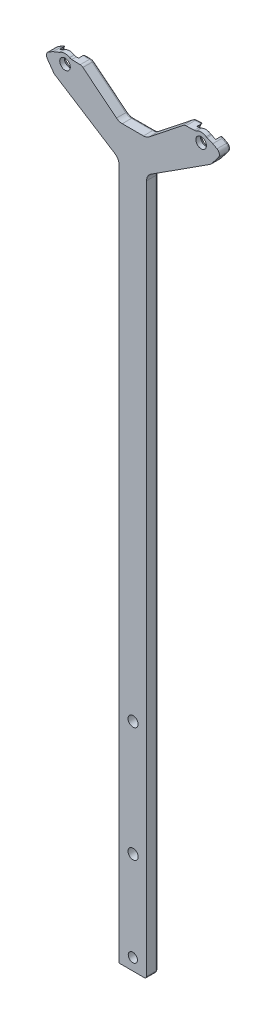
SolidWorks part; units mm, degrees
ref_plane "Płaszczyzna przednia" through (0, 0, 0) normal (0, 0, 1) x (1, 0, 0)
ref_plane "Płaszczyzna górna" through (0, 0, 0) normal (0, 1, 0) x (1, 0, 0)
ref_plane "Płaszczyzna prawa" through (0, 0, 0) normal (1, 0, 0) x (0, 0, -1)
sketch "Szkic1" plane through (0, 0, 158.2318) normal (0, 0, -1) x (-1, 0, 0)
  line L1 (11.9733, -23.8324) -> (17.9733, -23.8324)
  line L2 (11.9733, -23.8324) -> (11.9733, 126.5141)
  line L4 (17.9733, -23.8324) -> (17.9733, 126.5079)
  line L8 (12.6702, 134.6055) -> (17.2697, 134.6055)
  line L17 (3.4265, 141.1371) -> (1.5863, 141.2045)
  line L18 (26.424, 141.1367) -> (28.2508, 141.2)
  line L19 (-2.4001, 140.6758) -> (-1.1701, 141.1719)
  line L21 (32.3012, 140.6529) -> (31.0255, 141.1663)
  line L24 (25.8325, 140.917) -> (18.522, 135.0461)
  line L25 (4.0114, 140.9212) -> (11.4273, 135.0386)
  line L27 (-1.8525, 136.5015) -> (11.0555, 128.196)
  line L29 (31.9245, 136.4876) -> (18.8992, 128.195)
  line L30 (-2.4001, 140.6758) -> (-3.3279, 140.1722)
  line L31 (-3.6355, 138.6735) -> (-2.1257, 136.7621)
  line L32 (32.3012, 140.6529) -> (33.2355, 140.1438)
  line L33 (33.5729, 138.6876) -> (32.2285, 136.7901)
  circle A0 centre (14.9235, 23.2256) radius 1.1 construction
  circle A1 centre (14.9235, -1.7745) radius 1.1 construction
  circle A2 centre (14.9733, -21.2743) radius 1 construction
  circle A3 centre (14.9235, 23.2256) radius 1.1
  circle A4 centre (14.9235, -1.7745) radius 1.1
  circle A5 centre (14.9733, -21.2743) radius 1
  circle A8 centre (0.1233, 139.6055) radius 1.15
  circle A9 centre (29.7233, 139.6055) radius 1.15
  arc A12 (1.1231, 141.3377) -> (-0.9884, 141.2681) centre (0.1233, 139.6055) ccw
  arc A13 (30.8404, 141.2645) -> (28.7185, 141.3348) centre (29.7233, 139.6055) ccw
  arc A14 (-2.1257, 136.7621) -> (-1.8525, 136.5015) centre (-1.3114, 137.3424) ccw
  arc A15 (3.4265, 141.1371) -> (4.0114, 140.9212) centre (3.3899, 140.1378) cw
  arc A16 (1.1231, 141.3377) -> (1.5863, 141.2045) centre (1.6229, 142.2038) ccw
  arc A17 (-1.1701, 141.1719) -> (-0.9884, 141.2681) centre (-1.5442, 142.0993) ccw
  arc A18 (-2.6, 140.5673) -> (-2.4001, 140.6758) centre (-2.026, 139.7484) cw
  arc A19 (31.9245, 136.4876) -> (32.2285, 136.7901) centre (31.3875, 137.3312) ccw
  arc A20 (31.0255, 141.1663) -> (30.8404, 141.2645) centre (31.3989, 142.094) cw
  arc A21 (28.2508, 141.2) -> (28.7185, 141.3348) centre (28.2161, 142.1994) ccw
  arc A22 (25.8325, 140.917) -> (26.424, 141.1367) centre (26.4587, 140.1373) cw
  arc A23 (32.505, 140.5418) -> (32.3012, 140.6529) centre (31.9279, 139.7252) ccw
  arc A24 (17.2697, 134.6055) -> (18.522, 135.0461) centre (17.2697, 136.6055) ccw
  arc A25 (12.6702, 134.6055) -> (11.4273, 135.0386) centre (12.6702, 136.6055) cw
  arc A26 (11.9733, 126.5141) -> (11.0555, 128.196) centre (9.9733, 126.5141) ccw
  arc A27 (17.9733, 126.5079) -> (18.8992, 128.195) centre (19.9733, 126.5079) cw
  arc A28 (33.5729, 138.6876) -> (33.2355, 140.1438) centre (32.757, 139.2657) ccw
  arc A29 (-3.6355, 138.6735) -> (-3.3279, 140.1722) centre (-2.8508, 139.2933) cw
  point P20 (-1.0142, 136.6055)
  point P35 (1.3112, 141.2146)
  point P40 (-1.0645, 141.2146)
  point P46 (31.1097, 136.6055)
  point P49 (30.9178, 141.2097)
  point P52 (28.5289, 141.2097)
  point P59 (17.9733, 134.6055)
  point P62 (11.9733, 134.6055)
  point P65 (11.9733, 127.6055)
  point P68 (17.9733, 127.6055)
  point P69 (0, 0)
  point P74 (34.2233, 139.6055)
  point P77 (-4.3717, 139.6055)
  dimension "D5" = 2
  dimension "D11" = 1
  dimension "D1" = 3
  dimension "D2" = 3
  dimension "D7" = 9
  dimension "D8" = 9
extrude "Dodanie-wyciągnięcie3" add sketch "Szkic1" along normal blind 2.5 contours A29 L31 A14 L27 A26 L2 L1 L4 A27 L29 A19 L33 A28 L32 L21 A20 A13 A21 L18 A22 L24 A24 L8 A25 L25 A15 L17 A16 A12 A17 L19 L30 A9 A8 A5 A4 A3 region at (-14.9831, 70.1288, 158.2318)
sketch "Szkic4" plane through (0, 0, 155.7318) normal (0, 0, -1) x (-1, 0, 0)
  circle A0 centre (0.1233, 139.6055) radius 2.5
  circle A1 centre (29.7233, 139.6055) radius 2.5
  dimension "D1" = 5
  dimension "D2" = 5
extrude "Wytnij-wyciągnięcie2" cut sketch "Szkic4" against normal blind 1.5
fillet "Zaokrąglenie3" radius 0.5 22 edges at (-27.1043, 141.1603, 155.7318) (-26.1105, 141.0747, 155.7318) (-2.743, 141.1622, 155.7318) (-3.7362, 141.0759, 155.7318) (-7.7193, 137.9799, 155.7318) (-12.0121, 134.7169, 155.7318) (-14.9699, 134.6055, 155.7318) (-17.9334, 134.7189, 155.7318) (2.8806, 137.7178, 155.7318) (3.8304, 139.4944, 155.7318) (-32.7683, 140.3983, 155.7318) (-33.7312, 139.4915, 155.7318) (-32.0929, 136.6224, 155.7318) (-17.9733, 51.3378, 155.7318) (-18.22, 127.4701, 155.7318) (-14.9733, -23.8324, 155.7318) (-22.1772, 137.9815, 155.7318) (2.864, 140.424, 155.7318) (-0.3509, 137.1159, 155.7318) (-29.497, 137.1158, 155.7318) (-32.9007, 137.7388, 155.7318) (-25.4119, 132.3413, 155.7318)
fillet "Zaokrąglenie4" radius 0.5 6 edges at (2.2639, 137.0379, 155.7318) (-11.9733, -23.8324, 157.2318) (-11.9733, -23.6859, 155.8783) (-11.9733, 51.5909, 155.7318) (-11.7289, 127.4721, 155.7318) (-4.6015, 132.3488, 155.7318)
sketch "Szkic6" plane through (0, 0, 155.7318) normal (0, 0, -1) x (-1, 0, 0)
  line L0 (12.6702, 134.6055) -> (17.2697, 134.6055) construction
  line L1 (15.085, 128.6055) -> (15.085, 132.6055) construction
  line L2 (15.085, 128.6055) -> (15.085, 132.6055)
  arc A0 (15.085, 132.6055) -> (15.085, 128.6055) centre (15.085, 130.6055) ccw
  dimension "D1" = 4
  dimension "D2" = 4
revolve "Obrót7" add sketch "Szkic6" angle 180 about L1
